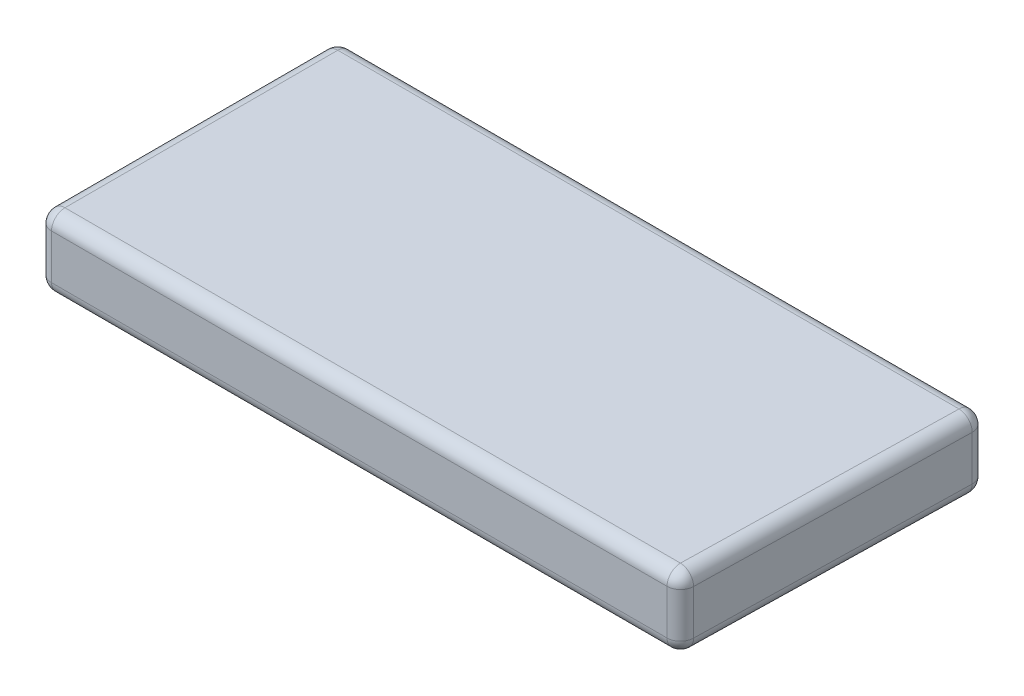
SolidWorks part; units mm, degrees
ref_plane "Front Plane" through (0, 0, 0) normal (0, 0, 1) x (1, 0, 0)
ref_plane "Top Plane" through (0, 0, 0) normal (0, 1, 0) x (1, 0, 0)
ref_plane "Right Plane" through (0, 0, 0) normal (1, 0, 0) x (0, 0, -1)
sketch "Sketch2" plane through (0, 0, 0) normal (0, 1, 0) x (1, 0, 0)
  line L4 (-72.4956, -0.7992) -> (-72.4956, 33.5)
  line L5 (-72.4956, 33.5) -> (72.4956, 33.5)
  line L6 (72.4956, 33.5) -> (71.0702, -33.5)
  line L7 (71.0702, -33.5) -> (-72.4956, -33.5)
  line L8 (-72.4956, -33.5) -> (-72.4956, -0.7992)
extrude "Boss-Extrude2" add sketch "Sketch2" along normal blind 8 and the other way blind 8 contours L5 L6 L7 L8 L4
sketch "Sketch3" plane through (-72.4956, 0, 0) normal (-1, 0, 0) x (0, 0, 1)
  line L0 (-33.5, -8) -> (-33.5, 8) construction
  line L1 (-4.47, 0) -> (4.47, 0) construction
  line L2 (-23.5, -2.4283) -> (-23.5, 2.5717)
  line L3 (-23.5, 2.5717) -> (-11, 2.5717)
  line L4 (-11, 2.5717) -> (-11, -2.4283)
  line L5 (-11, -2.4283) -> (-23.5, -2.4283)
  line L6 (23.5, -2.4283) -> (23.5, 2.5717)
  line L7 (23.5, 2.5717) -> (11, 2.5717)
  line L8 (11, 2.5717) -> (11, -2.4283)
  line L9 (11, -2.4283) -> (23.5, -2.4283)
  line L10 (33.5, -8) -> (33.5, 8) construction
  line L11 (0, 1.605) -> (0, -1.605) construction
  line L14 (-4.47, 1.605) -> (4.47, 1.605)
  line L15 (4.47, 1.605) -> (4.47, -1.605)
  line L16 (4.47, -1.605) -> (-4.47, -1.605)
  line L17 (-4.47, -1.605) -> (-4.47, 1.605)
  point P2 (-33.5, 0)
  point P17 (0, 0)
  point P26 (0, 0)
  point P27 (0, 0)
  point P28 (-3.2885, 0.3987)
  point P29 (0, 0)
  point P30 (0, 0)
  dimension "D1" = 10
  dimension "D2" = 12.5
  dimension "D3" = 5
  dimension "D4" = 12.5
  dimension "D5" = 5
  dimension "D6" = 10
  dimension "D7" = 8.94
  dimension "D8" = 1.605
  dimension "D9" = 3.21
extrude "Cut-Extrude1" cut sketch "Sketch3" against normal blind 16
fillet "Fillet1" radius 3 12 edges at (72.4956, 0, -33.5) (0, 8, -33.5) (-72.4956, 0, -33.5) (71.7829, -8, 0) (0, -8, -33.5) (-72.4956, -8, 0) (-0.7127, -8, 33.5) (-72.4956, 0, 33.5) (-0.7127, 8, 33.5) (71.0702, 0, 33.5) (71.7829, 8, 0) (-72.4956, 8, 0)
fillet "Fillet2" radius 1 8 edges at (-72.4956, 0.0717, 11) (-72.4956, 2.5717, 17.25) (-72.4956, 0.0717, 23.5) (-72.4956, -2.4283, 17.25) (-72.4956, -2.4283, -17.25) (-72.4956, 0.0717, -23.5) (-72.4956, 2.5717, -17.25) (-72.4956, 0.0717, -11)
fillet "Fillet3" radius 1.25 10 edges at (-72.4956, 1.605, 0) (-72.4956, 0, -4.47) (-72.4956, -1.605, 0) (-72.4956, 0, 4.47) (-64.4956, 1.605, -4.47) (-56.4956, 0, -4.47) (-64.4956, -1.605, -4.47) (-56.4956, -1.605, 0) (-64.4956, -1.605, 4.47) (-64.4956, 1.605, 4.47)
